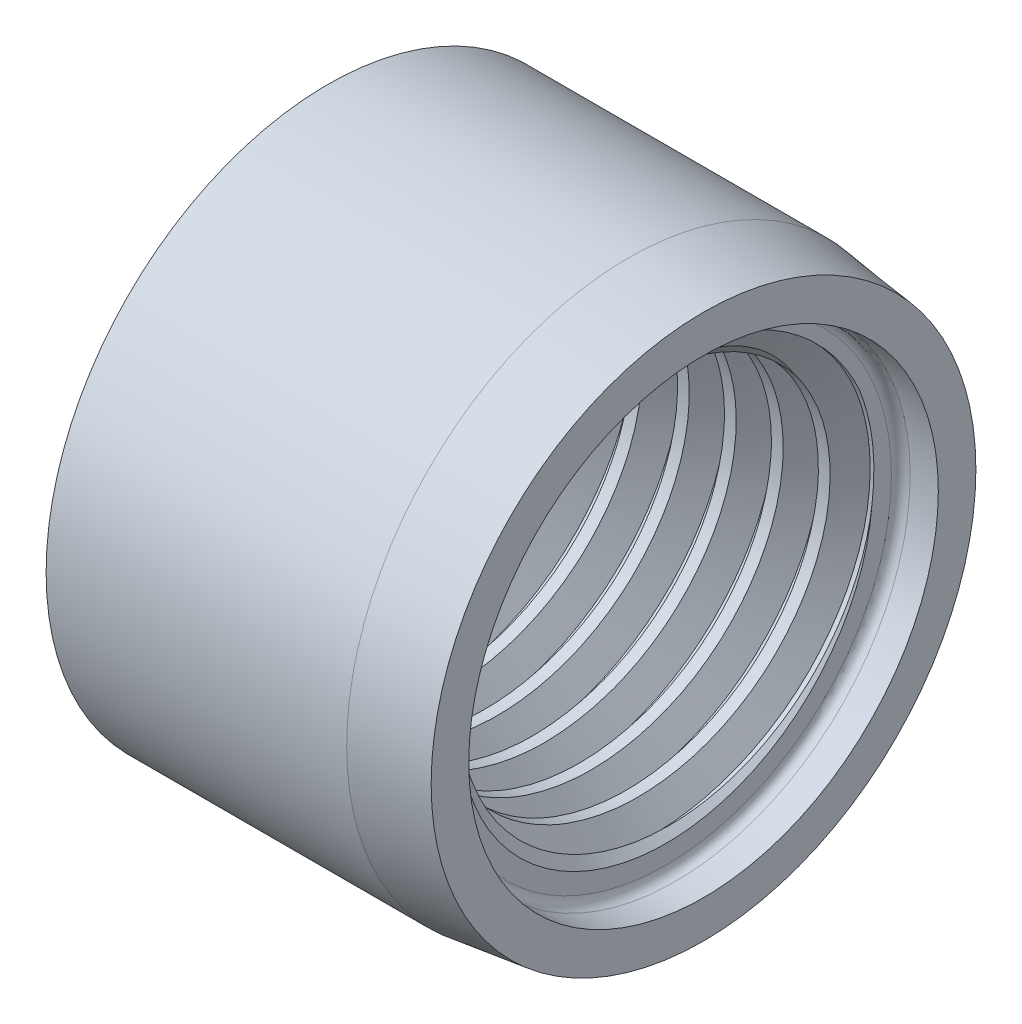
SolidWorks part; units mm, degrees
material "1.4404 (X2CrNiMo17-12-2)"
ref_plane "Front Plane" through (0, 0, 0) normal (0, 0, 1) x (1, 0, 0)
ref_plane "Top Plane" through (0, 0, 0) normal (0, 1, 0) x (1, 0, 0)
ref_plane "Right Plane" through (0, 0, 0) normal (1, 0, 0) x (0, 0, -1)
ref_axis "Axis1" through (-88.99, 0, 0) along (1, 0, 0)
sketch "Sketch1" plane through (0, 0, 0) normal (0, 0, 1) x (1, 0, 0)
  line L1 (0.866, 5) -> (8.5, 5)
  line L2 (0, 6.5) -> (0, 7.5)
  line L3 (0, 7.5) -> (8, 7.5)
  line L4 (10, 6.25) -> (10, 7.25)
  line L5 (-88.99, 0) -> (88.99, 0) construction
  line L6 (10, 6.25) -> (9.25, 6.25)
  line L7 (9, 6) -> (9, 5.5)
  line L10 (8, 7.5) -> (10, 7.25)
  line L11 (0, 6.5) -> (0.866, 5)
  line L12 (9, 5.5) -> (8.5, 5)
  arc A0 (9.25, 6.25) -> (9, 6) centre (9.25, 6) ccw
  point P0 (0, 5)
  point P11 (9, 5)
  dimension "D11" = 0.25
  dimension "D1" = 10
  dimension "D2" = 15
  dimension "D3" = 10
  dimension "D4" = 12.5
  dimension "D5" = 14.5
  dimension "D6" = 2
  dimension "D7" = 1
  dimension "D8" = 1.5
  dimension "D9" = 60
  dimension "D10" = 45
  dimension "D12" = 0.5
revolve "Revolve1" add sketch "Sketch1" angle 360 about axis through (-88.99, 0, 0) along (1, 0, 0)
thread "Thread2" pitch 1.25 method cut profile "Thread Profile2" start angle 0, offset 1.25, length 20, pitch 1.25, diameter 10
ref_plane "Plane2" through (-0.384, 0, -5) normal (0, -1, 0) x (0, 0, -1)
sketch "Thread Profile2" plane through (-0.384, 0, -5) normal (0, -1, 0) x (0, 0, -1)
  line L0 (0, 0) -> (0, 1.25) construction
  line L1 (0, 0) -> (0.6766, 0.3906)
  line L2 (0.6766, 0.3906) -> (0.6766, 0.5469)
  line L3 (0.6766, 0.5469) -> (0, 0.9375)
  line L4 (0.6766, 0.4687) -> (0, 0.4687) construction
  line L11 (0, 0) -> (0, 0.9375)
  point P2 (0, 0)
  dimension "Pitch" = 1.25
  dimension "Profile_Angle" = 60
  dimension "Profile_Land" = 0.1562
  dimension "Profile_Height" = 0.6766
